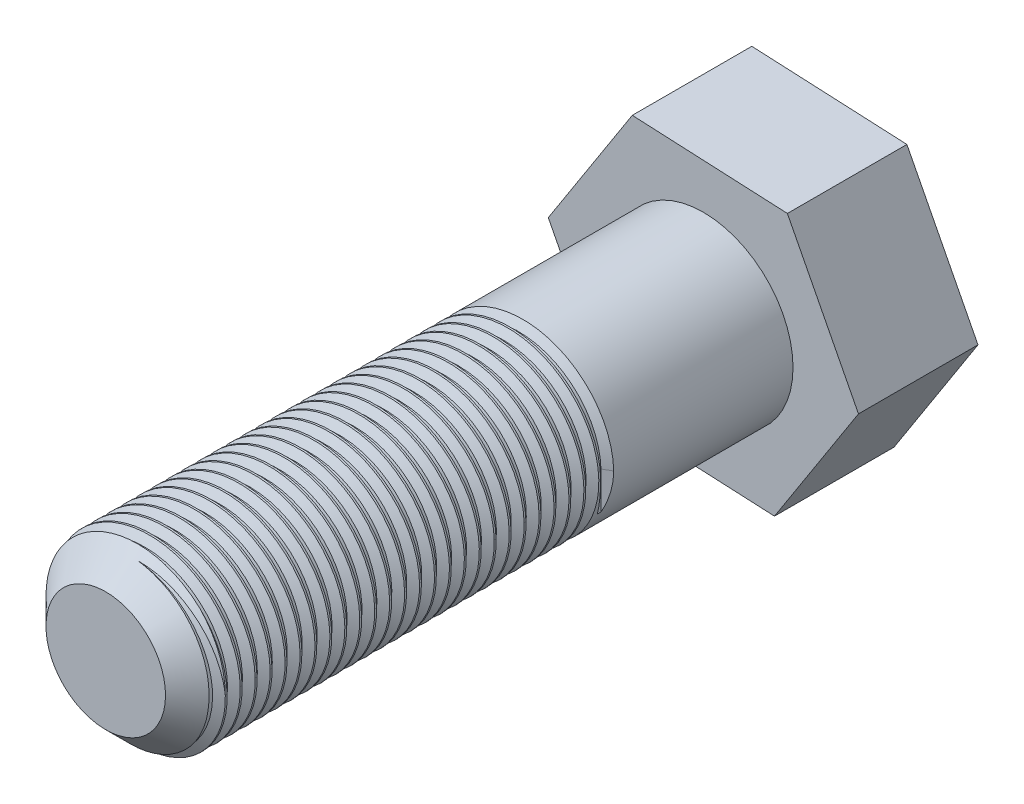
SolidWorks part; units mm, degrees
ref_plane "Front Plane" through (0, 0, 0) normal (0, 0, 1) x (1, 0, 0)
ref_plane "Top Plane" through (0, 0, 0) normal (0, 1, 0) x (1, 0, 0)
ref_plane "Right Plane" through (0, 0, 0) normal (1, 0, 0) x (0, 0, -1)
sketch "Sketch2" plane through (0, 0, 0) normal (0, 0, 1) x (1, 0, 0)
  line L1 (1.1896, -2.3097) -> (2.5951, -0.1246)
  line L2 (2.5951, -0.1246) -> (1.4055, 2.1851)
  line L3 (1.4055, 2.1851) -> (-1.1896, 2.3097)
  line L4 (-1.1896, 2.3097) -> (-2.5951, 0.1246)
  line L5 (-2.5951, 0.1246) -> (-1.4055, -2.1851)
  line L6 (-1.4055, -2.1851) -> (1.1896, -2.3097)
  circle A0 centre (0, 0) radius 2.25 construction
  dimension "D1" = 4.5
extrude "Boss-Extrude1" add sketch "Sketch2" along normal mid plane 2
sketch "Sketch4" plane through (0, 0, 1) normal (0, 0, 1) x (1, 0, 0)
  circle A0 centre (0, 0) radius 1.5
  dimension "D1" = 3
extrude "Boss-Extrude2" add sketch "Sketch4" along normal blind 10 contours A0
chamfer "Chamfer1" distance 0.5 angle 45 1 edges at (1.5, 0, 11)
thread "Thread1" pitch 0.25 method cut profile "Thread Profile1" start angle 0, offset 3, length 0, pitch 0.25, diameter 3
ref_plane "Plane1" through (1.5, 0, 4) normal (0, -1, 0) x (1, 0, 0)
sketch "Thread Profile1" plane through (1.5, 0, 4) normal (0, -1, 0) x (1, 0, 0)
  line L0 (0, 0) -> (0, 0.25) construction
  line L11 (0, 0) -> (0, 0.2187)
  line L12 (0, 0.2187) -> (-0.1353, 0.1406)
  line L13 (-0.1353, 0.1406) -> (-0.1353, 0.0781)
  line L15 (-0.1353, 0.0781) -> (0, 0)
  line L17 (-0.1353, 0.1094) -> (0, 0.1094) construction
  point P2 (0, 0)
  dimension "Pitch" = 0.25
  dimension "Profile_Angle" = 60
  dimension "Profile_Land" = 0.0625
  dimension "Profile_Height" = 0.1353
sketch "Sketch10" plane through (0, 0, 0) normal (0, 1, 0) x (1, 0, 0)
  line L4 (1.5, -4) -> (1.3647, -4.0781)
  line L5 (1.3647, -4.0781) -> (1.3647, -4.1406)
  line L6 (1.3647, -4.1406) -> (1.5, -4.2187)
  line L7 (1.5, -4.2187) -> (1.5, -4)
  line L8 (1.5, -4) -> (1.3647, -4.0781)
  line L9 (1.3647, -4.0781) -> (1.3647, -4.1406)
  line L10 (1.3647, -4.1406) -> (1.5, -4.2187)
  line L11 (1.5, -4.2187) -> (1.5, -4)
  dimension "D1" = 0
extrude "Cut-Extrude2" cut sketch "Sketch10" against normal through all
move or copy body "Body-Move/Copy1" [suppressed] bodies to move or copy 106
move or copy body "Body-Move/Copy2" [suppressed] bodies to move or copy 107
